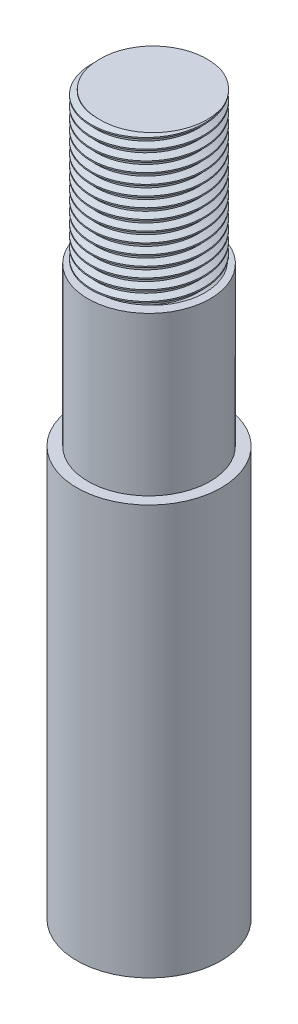
SolidWorks part; units mm, degrees
ref_plane "Front Plane" through (0, 0, 0) normal (0, 0, 1) x (1, 0, 0)
ref_plane "Top Plane" through (0, 0, 0) normal (0, 1, 0) x (1, 0, 0)
ref_plane "Right Plane" through (0, 0, 0) normal (1, 0, 0) x (0, 0, -1)
sketch "Sketch6" plane through (0, 0, 0) normal (0, 0, 1) x (1, 0, 0)
  line L0 (0, 0) -> (-10.05, 0)
  line L2 (0, 0) -> (0, 100)
  line L3 (0, 100) -> (-7.0714, 100)
  line L6 (-8.5, 79) -> (-7.0714, 79)
  line L7 (-7.0714, 79) -> (-7.0714, 100)
  line L10 (-8.5, 79) -> (-8.5, 57)
  line L16 (-10.05, 0) -> (-10.05, 57)
  line L17 (-10.05, 57) -> (-8.5, 57)
  dimension "D6" = 100
  dimension "D3" = 21
  dimension "D2" = 7.0714
  dimension "D1" = 8.5
  dimension "D4" = 10.05
  dimension "D5" = 22
revolve "Revolve1" add sketch "Sketch6" angle 360 about L2
thread "Thread1" pitch 1.4111 start angle 0, offset 0.0001, length 24, pitch 1.4111, diameter 14.1427
ref_plane "Plane2" through (-7.0714, 101.0582, 0) normal (0, 0, 1) x (-1, 0, 0)
sketch "Thread Profile2" plane through (-7.0714, 101.0582, 0) normal (0, 0, 1) x (-1, 0, 0)
  line L0 (0, 0) -> (0, 1.4111) construction
  line L1 (0, 0) -> (0.7638, 0.441)
  line L2 (0.7638, 0.441) -> (0.7638, 0.6174)
  line L3 (0.7638, 0.6174) -> (0, 1.0583)
  line L4 (0.7638, 0.5292) -> (0, 0.5292) construction
  line L11 (0, 0) -> (0, 1.0583)
  point P2 (0, 0)
  dimension "Pitch" = 1.4111
  dimension "Profile_Angle" = 60
  dimension "Profile_Land" = 0.1764
  dimension "Profile_Height" = 0.7638
equation "\"Turbine_Cx\"= 23.74"
equation "\"Bearing_d\"= 17"
equation "\"Bearing_d1\"= 22.7"
equation "\"D2@Sketch6\"=0.5568in / 2"
